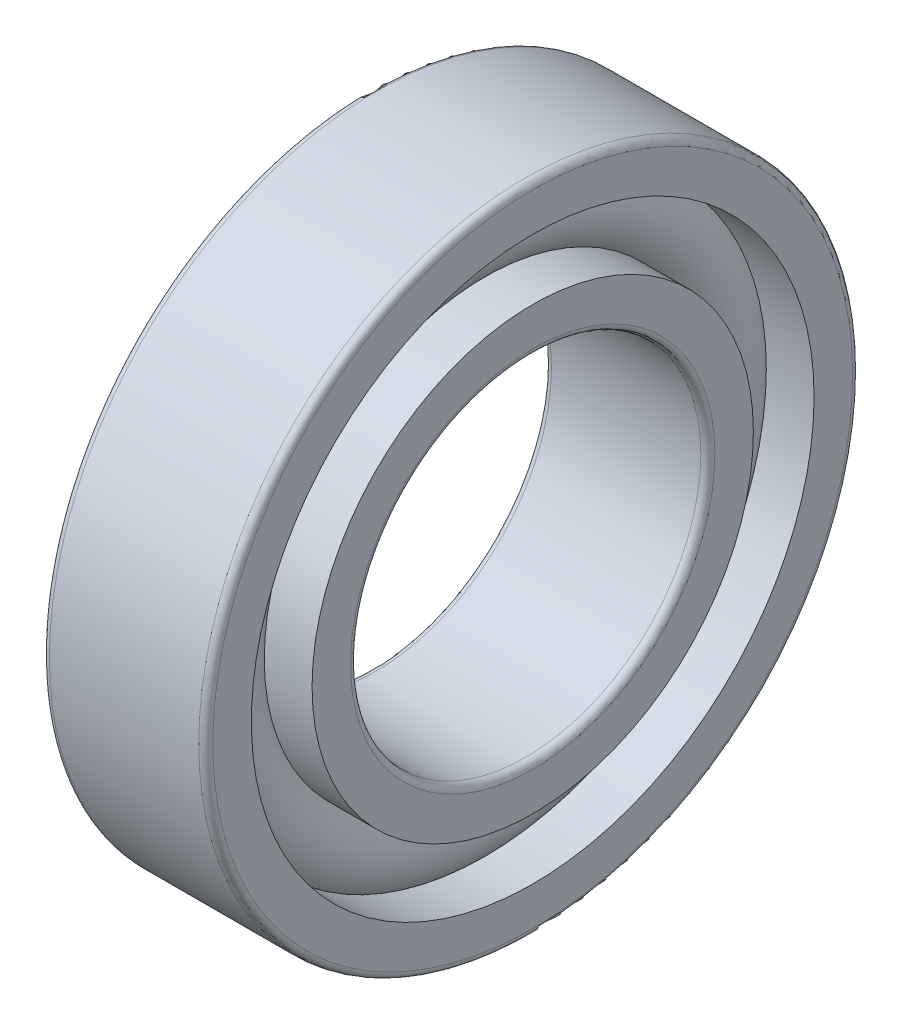
SolidWorks part; units mm, degrees
material "65Mn"
ref_plane "Plane1" through (0, 0, 0) normal (0, 0, 1) x (1, 0, 0)
ref_plane "Plane2" through (0, 0, 0) normal (0, 1, 0) x (1, 0, 0)
ref_plane "Plane3" through (0, 0, 0) normal (1, 0, 0) x (0, 0, -1)
sketch "Clipboard" plane through (0, 0, 0) normal (0, 0, 1) x (1, 0, 0)
  line L0 (-10, 0) -> (10, 0) construction
  line L1 (0, 0) -> (22.3471, -0.7804)
  line L2 (0, 0) -> (10.7435, 0.3752)
  line L3 (0, 0) -> (22.3471, -0.7804)
  line L4 (0, 0) -> (-22.3573, -0.3902)
  dimension "BallCLRad" = 10.75
sketch "CagSpiSke" plane through (0, 0, 0) normal (0, 0, 1) x (1, 0, 0)
  line L0 (0.195, 10.425) -> (0.195, 11.075)
  line L1 (0.195, 11.075) -> (-0.195, 11.075)
  line L2 (-0.195, 11.075) -> (-0.195, 10.425)
  line L3 (-0.195, 10.425) -> (0.195, 10.425)
  line L4 (-20.6375, 0) -> (20.6375, 0) construction
  line L5 (0, 0) -> (0, 23.7692) construction
  dimension "OD" = 22.15
  dimension "ID" = 20.85
revolve "CageSpine" add sketch "CagSpiSke" angle 0.001 about L4 reverse direction yes
ref_axis "Axis1" through (-50, 0, 0) along (1, 0, 0)
sketch "CagBalSke" plane through (0, 0, 0) normal (0, 0, 1) x (1, 0, 0)
  line L0 (-2.145, 10.75) -> (2.145, 10.75)
  line L1 (-1.905, 10.75) -> (1.905, 10.75) construction
  line L2 (-10, 0) -> (10, 0) construction
  line L3 (0, 0) -> (0, 24) construction
  arc A0 (2.145, 10.75) -> (-2.145, 10.75) centre (0, 10.75) cw
  dimension "BallCLRad" = 10.75
revolve "CageBall" [suppressed] add sketch "CagBalSke" angle 360 about L1 reverse direction yes
pattern_circular "CageBalls" [suppressed] count 2 every 180 about axis through (-50, 0, 0) along (1, 0, 0)
sketch "CagTrmODSke" plane through (0, 0, 0) normal (0, 0, 1) x (1, 0, 0)
  line L0 (2.146, 11.075) -> (2.146, 12.896)
  line L1 (2.146, 12.896) -> (-2.146, 12.896)
  line L2 (-2.146, 12.896) -> (-2.146, 11.075)
  line L3 (-2.146, 11.075) -> (2.146, 11.075)
  line L4 (-20.6375, 0) -> (20.6375, 0) construction
  line L5 (0, 0) -> (0, 25) construction
  dimension "Width" = 4.292
  dimension "ID" = 22.15
  dimension "OD" = 25.792
revolve "CageTrimOD" [suppressed] cut sketch "CagTrmODSke" angle 360 about L4 reverse direction yes
sketch "CagTrmIDSke" plane through (0, 0, 0) normal (0, 0, 1) x (1, 0, 0)
  line L0 (2.146, 8.606) -> (2.146, 10.425)
  line L1 (2.146, 10.425) -> (-2.146, 10.425)
  line L2 (-2.146, 10.425) -> (-2.146, 8.606)
  line L3 (-2.146, 8.606) -> (2.146, 8.606)
  line L4 (-20.6375, 0) -> (20.6375, 0) construction
  line L5 (0, 0) -> (0, 25) construction
  dimension "Width" = 4.292
  dimension "ID" = 17.212
  dimension "OD" = 20.85
revolve "CageTrimID" [suppressed] cut sketch "CagTrmIDSke" angle 360 about L4 reverse direction yes
sketch "BalSimSke" plane through (0, 0, 0) normal (0, 0, 1) x (1, 0, 0)
  line L0 (-10, 0) -> (10, 0) construction
  line L1 (-10, 10.75) -> (10, 10.75) construction
  line L2 (0, 0) -> (0, 23) construction
  circle A0 centre (0, 10.75) radius 1.95
  dimension "BallCLRad" = 10.75
  dimension "Ball_diameter" = 3.9
revolve "BallsSimplified" add sketch "BalSimSke" angle 360 about L0
sketch "BalDetSke" plane through (0, 0, 0) normal (0, 0, 1) x (1, 0, 0)
  line L0 (-1.95, 10.75) -> (1.95, 10.75)
  line L1 (-1.905, 10.75) -> (1.905, 10.75) construction
  line L2 (0, 0) -> (0, 25) construction
  arc A0 (1.95, 10.75) -> (-1.95, 10.75) centre (0, 10.75) cw
  dimension "BallCLRad" = 10.75
  dimension "Ball_diameter" = 3.9
revolve "BallDetailed" [suppressed] add sketch "BalDetSke" angle 360 about L1 reverse direction yes
sketch "InnRacSke" plane through (0, 0, 0) normal (0, 0, 1) x (1, 0, 0)
  line L0 (-1.4197, 9.45) -> (-3.5, 9.45)
  line L1 (-3.5, 9.45) -> (-3.5, 7.8)
  line L2 (-3.2, 7.5) -> (3.2, 7.5)
  line L3 (3.5, 7.8) -> (3.5, 9.45)
  line L4 (3.5, 9.45) -> (1.4197, 9.45)
  line L5 (-20.6375, 0) -> (20.6375, 0) construction
  line L6 (0, 0) -> (0, 30) construction
  arc A0 (-3.5, 7.8) -> (-3.2, 7.5) centre (-3.2, 7.8) ccw
  arc A1 (3.2, 7.5) -> (3.5, 7.8) centre (3.2, 7.8) ccw
  arc A2 (1.4197, 9.45) -> (-1.4197, 9.45) centre (0, 10.75) cw
  dimension "BallCLRad" = 10.75
  dimension "Fillet_radius" = 0.3
  dimension "Ball_diameter" = 3.85
  dimension "ID" = 15
  dimension "OD" = 18.9
  dimension "Width" = 7
revolve "InnerRace" add sketch "InnRacSke" angle 360 about L5 reverse direction yes
sketch "OutRacSke" plane through (0, 0, 0) normal (0, 0, 1) x (1, 0, 0)
  line L0 (-1.4197, 12.05) -> (-3.5, 12.05)
  line L1 (-3.5, 12.05) -> (-3.5, 13.7)
  line L2 (-3.2, 14) -> (3.2, 14)
  line L3 (3.5, 13.7) -> (3.5, 12.05)
  line L4 (3.5, 12.05) -> (1.4197, 12.05)
  line L5 (-20.6375, 0) -> (20.6375, 0) construction
  line L6 (0, 0) -> (0, 30) construction
  arc A0 (-3.5, 13.7) -> (-3.2, 14) centre (-3.2, 13.7) cw
  arc A1 (3.2, 14) -> (3.5, 13.7) centre (3.2, 13.7) cw
  arc A2 (1.4197, 12.05) -> (-1.4197, 12.05) centre (0, 10.75) ccw
  dimension "BallCLRad" = 10.75
  dimension "Fillet_radius" = 0.3
  dimension "Ball_diameter" = 3.85
  dimension "Width" = 7
revolve "OuterRace" add sketch "OutRacSke" angle 360 about L5 reverse direction yes
pattern_circular "BallsDetailed" [suppressed] count 2 every 180 about axis through (-50, 0, 0) along (1, 0, 0)
equation "\"BallCLRad@Clipboard\" = ( \"OD@OutRacSke\" + \"ID@InnRacSke\" ) / 4"
equation "\"BallCLRad@BalSimSke\" = \"BallCLRad@Clipboard\""
equation "\"BallCLRad@BalDetSke\" = \"BallCLRad@Clipboard\""
equation "\"BallCLRad@InnRacSke\" = \"BallCLRad@Clipboard\""
equation "\"BallCLRad@OutRacSke\" = \"BallCLRad@Clipboard\""
equation "\"Ball_diameter@InnRacSke\" = \"Ball_diameter@BalDetSke\" - 0.05"
equation "\"Ball_diameter@OutRacSke\" = \"Ball_diameter@BalDetSke\" - 0.05"
equation "\"Ball_diameter@BalSimSke\" = \"Ball_diameter@BalDetSke\""
equation "\"Width@OutRacSke\" = \"Width@InnRacSke\""
equation "\"Fillet_radius@OutRacSke\" = \"Fillet_radius@InnRacSke\""
equation "\"Max_count@Clipboard\" = int( 3.14159265 / atn(( \"Ball_diameter@BalDetSke\" / 2) / sqr( \"BallCLRad@Clipboard\"  *  \"BallCLRad@Clipboard\" - ( \"Ball_diameter@BalDetSke\" / 2) *  ( \"Ball_diameter@BalDetSke\" / 2))))"
equation "\"Max_count@Clipboard\" = ((sgn( \"Max_count@Clipboard\" - \"Count@Clipboard\" )-1)*( \"Max_count@Clipboard\" - \"Count@Clipboard\" ))/-2+ \"Count@Clipboard\""
equation "\"Count@BallsDetailed\" = int( \"Show_count@Clipboard\" ) "
equation "\"Count@BallsDetailed\" = ((sgn( \"Count@BallsDetailed\" - \"Max_count@Clipboard\" )-1)*( \"Count@BallsDetailed\" - \"Max_count@Clipboard\" ))/-2+ \"Max_count@Clipboard\""
equation "\"Count@BallsDetailed\" = ((sgn( \"Count@BallsDetailed\" - \"Min_count@Clipboard\" )+1)*( \"Count@BallsDetailed\" - \"Min_count@Clipboard\"))/2 +\"Min_count@Clipboard\""
equation "\"Angle@BallsDetailed\" = 360.0 / \"Max_count@Clipboard\""
equation "\"BallCLRad@CagBalSke\" = \"BallCLRad@Clipboard\""
equation "\"Count@CageBalls\" = \"Count@BallsDetailed\""
equation "\"Angle@CageBalls\" = \"Angle@BallsDetailed\""
equation "\"Angle@CageSpine\" =  \"Angle@CageBalls\" * ( \"Count@CageBalls\" -1 + int( \"Count@CageBalls\" / \"Max_count@Clipboard\" ) )  + 0.001 -  int( \"Count@CageBalls\" / \"Max_count@Clipboard\" ) * 0.001"
equation "\"Angle@CageSpine\" =  \"Angle@CageSpine\" * int( \"Min_count@Clipboard\" / 2) + int(1 / \"Min_count@Clipboard\")  * 0.001"
equation "\"CageWallOD@CagBalSke\" =  \"Ball_diameter@BalDetSke\" * 1.1"
equation "\"Thickness@CagSpiSke\" =  \"Ball_diameter@BalDetSke\" * 0.1"
equation "\"OD@CagTrmODSke\" = \"BallCLRad@Clipboard\" * 2 + \"CageWallOD@CagBalSke\" + 0.002"
equation "\"ID@CagTrmODSke\" = \"BallCLRad@Clipboard\" * 2 + \"Ball_diameter@BalDetSke\" / 6"
equation "\"OD@CagTrmIDSke\" = \"BallCLRad@Clipboard\" * 2 - \"Ball_diameter@BalDetSke\" / 6"
equation "\"ID@CagTrmIDSke\" = \"BallCLRad@Clipboard\" * 2 - \"CageWallOD@CagBalSke\" + 0.002"
equation "\"OD@CagSpiSke\" = \"ID@CagTrmODSke\""
equation "\"ID@CagSpiSke\" = \"OD@CagTrmIDSke\""
equation "\"Width@CagTrmODSke\" = \"CageWallOD@CagBalSke\" + 0.002"
equation "\"Width@CagTrmIDSke\" = \"CageWallOD@CagBalSke\" + 0.002"
